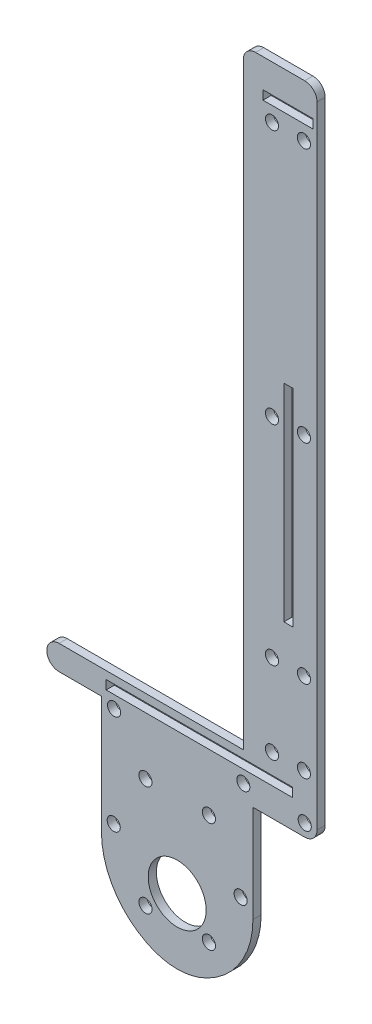
SolidWorks part; units mm, degrees
ref_plane "前视基准面" through (0, 0, 0) normal (0, 0, 1) x (1, 0, 0)
ref_plane "上视基准面" through (0, 0, 0) normal (0, 1, 0) x (1, 0, 0)
ref_plane "右视基准面" through (0, 0, 0) normal (1, 0, 0) x (0, 0, -1)
sketch "草图1" plane through (0, 0, 0) normal (0, 0, 1) x (1, 0, 0)
  line L0 (-45.6533, -106) -> (-45.6533, -80.5)
  line L1 (-11, -74.5) -> (11, -74.5)
  line L2 (-11, -74.5) -> (-11, 74.5)
  line L3 (-11, 74.5) -> (11, 74.5)
  line L4 (11, -74.5) -> (11, 74.5)
  line L5 (-11, -74.5) -> (11, 74.5) construction
  line L6 (-11, 74.5) -> (11, -74.5) construction
  line L7 (11, -74.5) -> (-59, -74.5)
  line L8 (11, -74.5) -> (11, -80.5)
  line L9 (11, -80.5) -> (-59, -80.5)
  line L10 (-59, -74.5) -> (-59, -80.5)
  line L11 (-45.6533, -106) -> (-45.6533, -109.2467)
  line L12 (-34.6655, -127.1011) -> (-27.1533, -130.893)
  line L13 (-8.6533, -106) -> (-8.6533, -80.5)
  line L14 (-8.6533, -106) -> (-8.6533, -109.2467)
  line L15 (-19.641, -127.1011) -> (-27.1533, -130.893)
  line L17 (-1.1, -42.5) -> (1.1, -42.5)
  line L18 (-1.1, -42.5) -> (-1.1, 8)
  line L19 (-1.1, 8) -> (1.1, 8)
  line L20 (1.1, -42.5) -> (1.1, 8)
  line L21 (-1.1, -42.5) -> (1.1, 8) construction
  line L22 (-1.1, 8) -> (1.1, -42.5) construction
  line L23 (-6.2, 67.5) -> (6, 67.5)
  line L24 (-6.2, 67.5) -> (-6.2, 65.3)
  line L25 (-6.2, 65.3) -> (6, 65.3)
  line L26 (6, 67.5) -> (6, 65.3)
  line L27 (-44.5, -76.4) -> (1, -76.4)
  line L28 (-44.5, -76.4) -> (-44.5, -78.6)
  line L29 (-44.5, -78.6) -> (1, -78.6)
  line L30 (1, -76.4) -> (1, -78.6)
  line L31 (-44.5, -76.4) -> (1, -78.6) construction
  line L32 (-44.5, -78.6) -> (1, -76.4) construction
  line L33 (11, -80.5) -> (-8.6533, -80.5)
  line L34 (11, -80.5) -> (11, -85.5)
  line L35 (11, -85.5) -> (-8.6533, -85.5)
  line L36 (-8.6533, -80.5) -> (-8.6533, -85.5)
  circle A0 centre (-27.1533, -113) radius 7.08
  arc A1 (-42.5707, -107.5979) -> (-36.2458, -118.5529) centre (-27.1533, -106) ccw
  circle A2 centre (-27.1533, -106) radius 18.5
  arc A3 (-36.2458, -93.4471) -> (-42.5707, -104.4021) centre (-27.1533, -106) ccw
  circle A4 centre (-34.9033, -92.5766) radius 1.6
  circle A5 centre (-19.4033, -92.5766) radius 1.6
  circle A6 centre (-11.6533, -106) radius 1.6
  circle A7 centre (-19.4033, -119.4234) radius 1.6
  circle A8 centre (-34.9033, -119.4234) radius 1.6
  circle A9 centre (-42.6533, -106) radius 1.6
  circle A10 centre (-4, 61.7) radius 1.6
  arc A11 (-20.8283, -91.8492) -> (-33.4782, -91.8492) centre (-27.1533, -106) ccw
  arc A12 (-11.7358, -104.4021) -> (-18.0608, -93.4471) centre (-27.1533, -106) ccw
  arc A13 (-18.0608, -118.5529) -> (-11.7358, -107.5979) centre (-27.1533, -106) ccw
  arc A14 (-33.4782, -120.1508) -> (-20.8283, -120.1508) centre (-27.1533, -106) ccw
  circle A15 centre (-4, -0.5) radius 1.6
  circle A16 centre (3.8, -0.5) radius 1.6
  circle A17 centre (3.8, 61.7) radius 1.6
  circle A18 centre (-4, -51.5) radius 1.6
  circle A19 centre (3.8, -51.5) radius 1.6
  circle A20 centre (-4, -71.5) radius 1.6
  circle A21 centre (3.8, -71.5) radius 1.6
  circle A22 centre (-42.5707, -81.6294) radius 1.6
  circle A23 centre (-11, -81.6294) radius 1.6
  arc A24 (-45.6533, -109.2467) -> (-34.6655, -127.1011) centre (-25.6533, -109.2467) ccw
  arc A25 (-34.3511, -127.2598) -> (-19.9554, -127.2598) centre (-27.1533, -113) ccw
  arc A26 (-8.6533, -109.2467) -> (-19.641, -127.1011) centre (-28.6533, -109.2467) cw
  point P0 (0, 0)
  point P20 (0, -17.25)
  point P30 (-21.75, -77.5)
  point P52 (0, 0)
  dimension "D7" = 7
  dimension "D8" = 50.5
  dimension "D19" = 3.6
  dimension "D23" = 20
  dimension "D1" = 22
  dimension "D2" = 149
  dimension "D3" = 70
  dimension "D4" = 6
  dimension "D5" = 38.1533
  dimension "D6" = 32.5
  dimension "D9" = 2.2
  dimension "D10" = 32
  dimension "D11" = 7
  dimension "D12" = 5
  dimension "D13" = 12.2
  dimension "D14" = 2.2
  dimension "D15" = 3
  dimension "D16" = 10
  dimension "D17" = 45.5
  dimension "D18" = 2.2
  dimension "D20" = 0
  dimension "D21" = 2.2
  dimension "D22" = 2.2
  dimension "D24" = 62.2
  dimension "D25" = 0
  dimension "D26" = 51
  dimension "D27" = 0
  dimension "D28" = 20
  dimension "D29" = 0
extrude "凸台-拉伸1" add sketch "草图1" along normal blind 2 contours A21 L1 L4 L3 L2 A20 A19 A18 A17 A16 A15 A10 L20 L17 L18 L19 L23 L26 L25 L24 | A23 L9 L8 L1 A21 A20 L7 L10 A22 L27 L30 L29 L28 | A23 L9 A22 L0 A2 L13 | A8 A14 A7 A13 A6 A12 A5 A11 A4 A3 A9 A1 A0 | A2 A14 A8 A1 A9 A3 A4 A11 A5 A12 A6 A13 A7 | A26 L14 A2 L11 A24 L12 A25 L15 | L35 L34 L9 L13 region at (-27.1533, -124.9355, 0) region at (-27.167, -86.9489, 0) region at (-27.1533, -88.0233, 0) region at (-52.3266, -79.7974, 0) region at (1.1734, -83, 0) region at (-9.4938, 0, 0) region at (-27.1533, -104.0785, 0)
sketch "草图2" plane through (0, 0, 0) normal (0, 0, -1) x (-1, 0, 0)
  line L0 (-11, -85.5) -> (8.6533, -85.5) construction
  line L1 (-11, 74.5) -> (-7, 74.5)
  line L2 (-11, 74.5) -> (-11, -85.5)
  line L3 (-11, -85.5) -> (-7, -85.5)
  line L4 (-7, 74.5) -> (-7, -85.5)
extrude "切除-拉伸1" cut sketch "草图2" against normal blind 10
sketch "草图3" plane through (0, 0, 0) normal (0, 0, -1) x (-1, 0, 0)
  line L0 (-7, -85.5) -> (-7, 74.5) construction
  line L2 (-7, -85.5) -> (8.6533, -85.5) construction
  circle A0 centre (-4, -82.5) radius 1.6
  dimension "D1" = 3
  dimension "D2" = 3
extrude "切除-拉伸2" cut sketch "草图3" against normal blind 10
fillet "圆角1" radius 3 5 edges at (7, 74.5, 1) (-11, 74.5, 1) (-59, -74.5, 1) (-59, -80.5, 1) (7, -85.5, 1)
